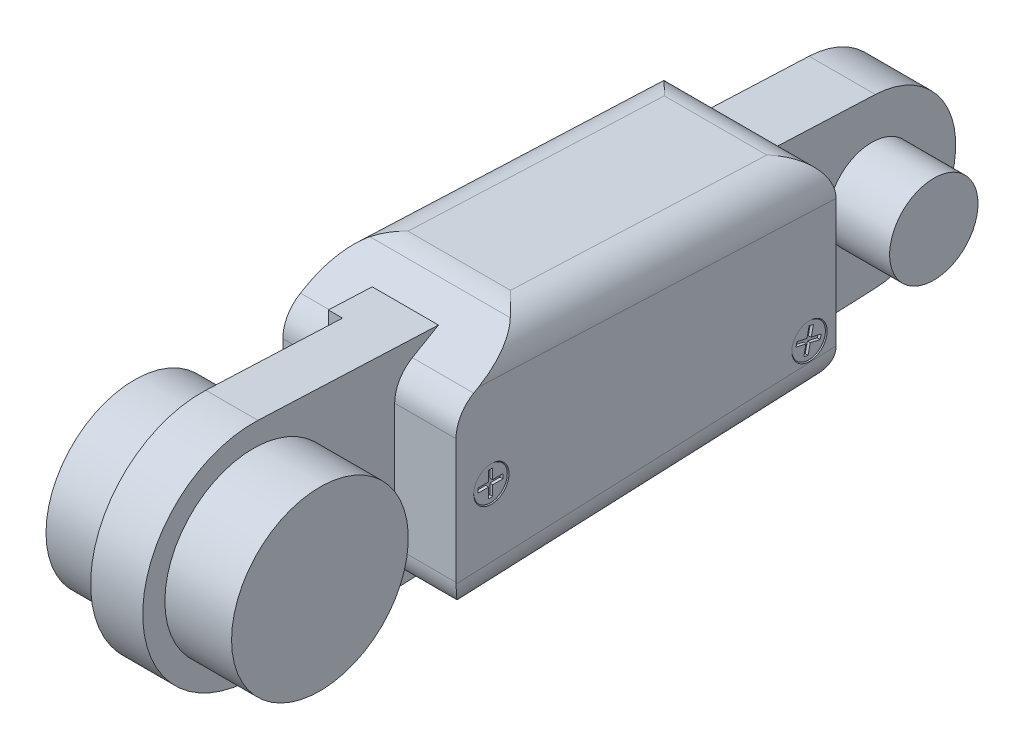
SolidWorks part; units mm, degrees
ref_plane "Front" through (0, 0, 0) normal (0, 0, 1) x (1, 0, 0)
ref_plane "Top" through (0, 0, 0) normal (0, 1, 0) x (1, 0, 0)
ref_plane "Right" through (0, 0, 0) normal (1, 0, 0) x (0, 0, -1)
sketch "Sketch1" plane through (0, 0, 0) normal (1, 0, 0) x (0, 0, -1)
  line L0 (0.5357, -12.4885) -> (70.4071, -9.4913)
  line L1 (0.5357, 12.4885) -> (70.4071, 9.4913)
  line L2 (0, 0) -> (70, 0) construction
  arc A0 (0.5357, 12.4885) -> (0.5357, -12.4885) centre (0, 0) ccw
  arc A1 (70.4071, 9.4913) -> (70.4071, -9.4913) centre (70, 0) cw
  dimension "D1" = 12.5
  dimension "D2" = 9.5
  dimension "D3" = 70
extrude "Boss-Extrude1" add sketch "Sketch1" along normal mid plane 5.9
sketch "Sketch2" plane through (-2.95, 0, 0) normal (-1, 0, 0) x (0, 0, 1)
  line L0 (-70.4071, 9.4913) -> (-0.5357, 12.4885) construction
  line L1 (-0.5357, -12.4885) -> (-70.4071, -9.4913) construction
  line L2 (-70.4071, 9.4913) -> (-16, 11.8252)
  line L3 (-16, -11.8252) -> (-70.4071, -9.4913)
  line L4 (-16, 11.8252) -> (-16, -11.8252)
  arc A0 (-70.4071, 9.4913) -> (-70.4071, -9.4913) centre (-70, 0) ccw construction
  arc A1 (-70.4071, 9.4913) -> (-70.4071, -9.4913) centre (-70, 0) ccw
  dimension "D1" = 16
extrude "Boss-Extrude2" add sketch "Sketch2" along normal blind 1.6
sketch "Sketch3" plane through (0, 0, 0) normal (1, 0, 0) x (0, 0, -1)
  circle A0 centre (0, 0) radius 10
  dimension "D1" = 20
extrude "Boss-Extrude3" add sketch "Sketch3" along normal mid plane 21
fillet "Fillet1" radius 4 1 edges
sketch "Sketch4" plane through (-4.55, 0, 0) normal (-1, 0, 0) x (0, 0, 1)
  line L0 (-16, -11.8252) -> (-16, 8.7452)
  line L2 (-25, 13.9414) -> (-59, 12.4829)
  line L3 (-59, 12.4829) -> (-59, -9.9806)
  line L4 (-16, 8.7452) -> (-25, 13.9414)
  line L5 (-59, -9.9806) -> (-16, -11.8252)
  line L6 (-16, 11.8252) -> (-70.4071, 9.4913) construction
  line L7 (-16, -7.6499) -> (-16, 11.8252) construction
  line L10 (-0.5357, -12.4885) -> (-20.1714, -11.6462) construction
  dimension "D1" = 43
  dimension "D2" = 2.5
  dimension "D3" = 60
  dimension "D4" = 9
extrude "Boss-Extrude4" add sketch "Sketch4" along normal blind 5.15 and the other way blind 14.45
sketch "Sketch6" plane through (0, -12.4885, -0.5357) normal (0, -0.9991, -0.0429) x (1, 0, 0)
  line L0 (-2.95, -15.4785) -> (-9.7, -15.4785) construction
  line L1 (-4.55, -60.4808) -> (-4.56, -60.4808)
  line L2 (-4.55, -60.4808) -> (-4.55, -15.4785)
  line L3 (-4.55, -15.4785) -> (-4.56, -15.4785)
  line L4 (-4.56, -60.4808) -> (-4.56, -15.4785)
  line L5 (-2.95, -15.4785) -> (-9.7, -15.4785) construction
  line L6 (2.95, -60.5181) -> (2.96, -60.5181)
  line L7 (2.95, -60.5181) -> (2.95, -15.4785)
  line L8 (2.95, -15.4785) -> (2.96, -15.4785)
  line L9 (2.96, -60.5181) -> (2.96, -15.4785)
  line L10 (2.95, -58.5181) -> (2.95, -69.9357) construction
  line L11 (9.9, -58.5181) -> (2.95, -58.5181) construction
  line L12 (-4.55, -69.9357) -> (-4.55, -58.5181) construction
  line L13 (9.9, -59.4808) -> (-9.7, -59.4808) construction
  dimension "D1" = 0.01
  dimension "D2" = 0.01
  dimension "D3" = 2
  dimension "D4" = 1
extrude "Cut-Extrude1" cut sketch "Sketch6" against normal offset from surface (18.3422 mm away) 1.5
fillet "Fillet2" radius 4 12 edges at (9.9, -10.9029, -37.5) (-9.7, -10.9029, -37.5) (9.9, 13.2121, -42) (-9.7, 13.2121, -42) (-7.13, -11.8252, -16) (-3.75, -11.8252, -16) (-7.13, -9.9806, -59) (6.43, -9.9806, -59) (0.1, 12.4829, -59) (6.43, -11.8252, -16) (6.43, 8.7452, -16) (0.1, 13.9414, -25)
sketch "Sketch7" plane through (2.95, 0, 0) normal (1, 0, 0) x (0, 0, -1)
  circle A0 centre (70, 0) radius 5
  dimension "D1" = 10
extrude "Boss-Extrude5" add sketch "Sketch7" along normal blind 7.02 and the other way blind 10.6
sketch "Sketch8" plane through (9.9, 0, 0) normal (1, 0, 0) x (0, 0, -1)
  line L0 (0, 0) -> (70, 0) construction
  line L1 (59, 8.4792) -> (59, -5.9769) construction
  circle A0 centre (20, 0) radius 2
  circle A1 centre (56, -4) radius 2
  dimension "D4" = 4
  dimension "D5" = 4
  dimension "D1" = 4
  dimension "D2" = 36
  dimension "D3" = 3
extrude "Cut-Extrude2" cut sketch "Sketch8" against normal blind 0.1 draft 45
sketch "Sketch9" plane through (9.8, 0, 0) normal (1, 0, 0) x (0, 0, -1)
  line L0 (20, 1.9) -> (20, 0) construction
  line L1 (20, 0) -> (21.9, 0) construction
  line L2 (20.25, -0.25) -> (20.25, -1.4)
  line L3 (20.25, 0.25) -> (21.4, 0.25)
  line L4 (20.25, 0.25) -> (20.25, -0.25) construction
  line L5 (20.25, -0.25) -> (21.4, -0.25)
  line L6 (21.4, 0.25) -> (21.4, -0.25)
  line L7 (20.25, 0.25) -> (21.4, -0.25) construction
  line L8 (20.25, -0.25) -> (21.4, 0.25) construction
  line L9 (20.25, -1.4) -> (19.75, -1.4)
  line L10 (19.75, -0.25) -> (19.75, -1.4)
  line L11 (19.75, -0.25) -> (18.6, -0.25)
  line L12 (18.6, -0.25) -> (18.6, 0.25)
  line L13 (19.75, 0.25) -> (18.6, 0.25)
  line L14 (19.75, 0.25) -> (19.75, 1.4)
  line L15 (19.75, 1.4) -> (20.25, 1.4)
  line L16 (20.25, 0.25) -> (20.25, 1.4)
  line L17 (20, 0) -> (56, -4) construction
  line L18 (38, -2) -> (38.5878, 3.2906) construction
  line L19 (55.7012, -4.189) -> (54.5793, -3.9366)
  line L20 (54.689, -3.4488) -> (54.5793, -3.9366)
  line L21 (55.811, -3.7012) -> (54.689, -3.4488)
  line L22 (55.811, -3.7012) -> (56.0634, -2.5793)
  line L23 (56.5512, -2.689) -> (56.0634, -2.5793)
  line L24 (56.2988, -3.811) -> (56.5512, -2.689)
  line L25 (56.2988, -3.811) -> (57.4207, -4.0634)
  line L26 (57.311, -4.5512) -> (57.4207, -4.0634)
  line L27 (56.189, -4.2988) -> (57.311, -4.5512)
  line L28 (56.189, -4.2988) -> (55.9366, -5.4207)
  line L29 (55.4488, -5.311) -> (55.9366, -5.4207)
  line L30 (55.7012, -4.189) -> (55.4488, -5.311)
  circle A0 centre (20, 0) radius 1.9 construction
  point P5 (20.825, 0)
  dimension "D1" = 0.5
  dimension "D2" = 0.25
  dimension "D3" = 1.4
  dimension "D4" = 4
extrude "Cut-Extrude3" cut sketch "Sketch9" against normal blind 0.3 draft 5
